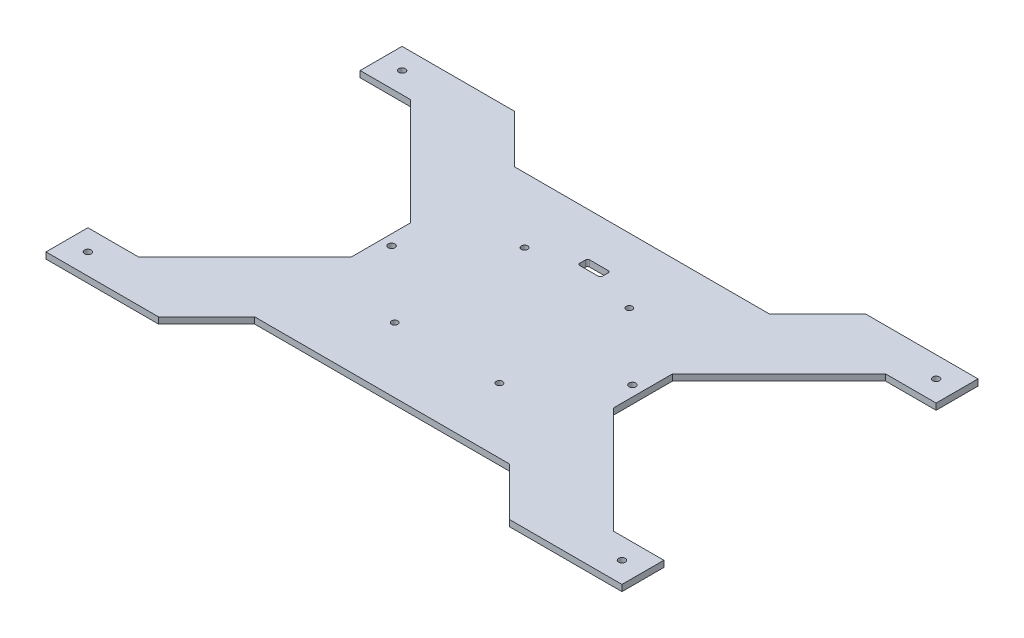
SolidWorks part; units mm, degrees
ref_plane "Front Plane" through (0, 0, 0) normal (0, 0, 1) x (1, 0, 0)
ref_plane "Top Plane" through (0, 0, 0) normal (0, 1, 0) x (1, 0, 0)
ref_plane "Right Plane" through (0, 0, 0) normal (1, 0, 0) x (0, 0, -1)
sketch "Sketch1" plane through (0, 0, 0) normal (0, -1, 0) x (1, 0, 0)
  line L0 (2.6321, -227.497) -> (-21.5101, -227.497)
  line L1 (-21.5101, -282.497) -> (-21.5101, 7.503) construction
  line L2 (-21.5101, -227.497) -> (-21.5101, -207.497)
  line L3 (-21.5101, -207.497) -> (32.1295, -207.497)
  line L4 (32.1295, -207.497) -> (55.0921, -230.4596)
  line L5 (55.0921, -230.4596) -> (176.8877, -230.4596)
  line L6 (53.4899, -292.497) -> (115.9899, -292.497) construction
  line L7 (115.9899, -230.4596) -> (115.9899, -292.497) construction
  line L8 (178.4899, -278.3549) -> (178.4899, -306.6392)
  line L9 (229.3478, -227.497) -> (178.4899, -278.3549)
  line L10 (253.4899, -227.497) -> (229.3478, -227.497)
  line L11 (253.4899, -207.497) -> (253.4899, -227.497)
  line L12 (199.8503, -207.497) -> (176.8877, -230.4596)
  line L13 (253.4899, -207.497) -> (199.8503, -207.497)
  line L14 (253.4899, -227.497) -> (253.4899, -207.497)
  line L15 (229.3478, -227.497) -> (253.4899, -227.497)
  line L16 (2.6321, -357.497) -> (53.4899, -306.6392)
  line L17 (-21.5101, -357.497) -> (2.6321, -357.497)
  line L18 (-21.5101, -377.497) -> (-21.5101, -357.497)
  line L19 (229.3478, -357.497) -> (253.4899, -357.497)
  line L20 (253.4899, -357.497) -> (253.4899, -377.497)
  line L21 (253.4899, -377.497) -> (199.8503, -377.497)
  line L22 (199.8503, -377.497) -> (176.8877, -354.5345)
  line L23 (253.4899, -377.497) -> (253.4899, -357.497)
  line L24 (253.4899, -357.497) -> (229.3478, -357.497)
  line L25 (229.3478, -357.497) -> (178.4899, -306.6392)
  line L26 (55.0921, -354.5345) -> (176.8877, -354.5345)
  line L27 (-21.5101, -357.497) -> (-21.5101, -432.2845)
  line L28 (-21.5101, -432.2845) -> (45.9899, -432.2845)
  line L29 (45.9899, -432.2845) -> (65.9899, -412.2845)
  line L30 (65.9899, -412.2845) -> (165.9899, -412.2845)
  line L31 (165.9899, -412.2845) -> (185.9899, -432.2845)
  line L32 (185.9899, -432.2845) -> (253.4899, -432.2845)
  line L33 (253.4899, -432.2845) -> (253.4899, -357.497)
  line L34 (253.4899, -357.497) -> (229.3478, -357.497)
  line L35 (229.3478, -357.497) -> (178.4899, -306.6392)
  line L36 (178.4899, -306.6392) -> (178.4899, -278.3549)
  line L37 (178.4899, -278.3549) -> (229.3478, -227.497)
  line L38 (229.3478, -227.497) -> (253.4899, -227.497)
  line L39 (253.4899, -227.497) -> (253.4899, -152.7096)
  line L40 (253.4899, -152.7096) -> (185.9899, -152.7096)
  line L41 (185.9899, -152.7096) -> (165.9899, -172.7096)
  line L42 (165.9899, -172.7096) -> (65.9899, -172.7096)
  line L43 (65.9899, -172.7096) -> (45.9899, -152.7096)
  line L44 (45.9899, -152.7096) -> (-21.5101, -152.7096)
  line L45 (-21.5101, -152.7096) -> (-21.5101, -227.497)
  line L46 (-21.5101, -227.497) -> (2.6321, -227.497)
  line L47 (2.6321, -227.497) -> (53.4899, -278.3549)
  line L48 (53.4899, -278.3549) -> (53.4899, -306.6392)
  line L49 (53.4899, -306.6392) -> (2.6321, -357.497)
  line L50 (2.6321, -357.497) -> (-21.5101, -357.497)
  line L69 (-21.5101, -207.497) -> (-21.5101, -227.497)
  line L70 (-21.5101, -227.497) -> (2.6321, -227.497)
  line L71 (2.6321, -227.497) -> (53.4899, -278.3549)
  line L72 (53.4899, -278.3549) -> (53.4899, -306.6392)
  line L75 (32.1295, -377.497) -> (55.0921, -354.5345)
  line L76 (-21.5101, -377.497) -> (32.1295, -377.497)
  line L77 (-21.5101, -357.497) -> (-21.5101, -377.497)
  line L78 (2.6321, -357.497) -> (-21.5101, -357.497)
  circle A0 centre (-11.5101, -217.497) radius 1.6
  circle A1 centre (243.4899, -217.497) radius 1.6
  circle A2 centre (243.4899, -367.497) radius 1.6
  circle A3 centre (-11.5101, -367.497) radius 1.6
  circle A4 centre (58.4899, -292.497) radius 1.6
  circle A5 centre (173.4899, -292.497) radius 1.6
  point P50 (178.4899, -292.497)
  line M31 (-1.5101, -302.497) -> (233.4899, -302.497)
  line M32 (233.4899, -302.497) -> (233.4899, -592.497)
  line M34 (-1.5101, -592.497) -> (-1.5101, -302.497)
  line M35 (233.4899, -282.497) -> (-1.5101, -282.497)
  line M36 (-1.5101, -282.497) -> (-1.5101, 7.503)
  line M38 (233.4899, 7.503) -> (233.4899, -282.497)
  line M39 (-21.5101, 7.503) -> (-21.5101, -282.497)
  line M43 (-21.5101, -302.497) -> (-21.5101, -592.497)
  line M49 (253.4899, -592.497) -> (253.4899, -302.497)
  line M53 (253.4899, -282.497) -> (253.4899, 7.503)
  dimension "D4" = 3.2
  dimension "D5" = 5
  dimension "D6" = 5
  dimension "D2" = 20
  dimension "D3" = 35
  dimension "D1" = 0
extrude "Extrude2" add sketch "Sketch1" along normal blind 3 contours L76 L17 A3 M43 M34 | L76 L75 L26 L22 L21 L19 L25 L8 L72 L16 L17 M34 M32 M31 | L21 L19 A2 M49 M32 | L72 L8 A5 A4 M35 M31 | L71 L72 L8 L9 L10 L13 L12 L5 L4 L3 L0 M35 M38 M36 | L3 L0 A0 M39 M36 | L13 L10 A1 M53 M38 region at (115.9899, 0, -247.4505) region at (-11.5101, 0, -227.2142) region at (115.9899, 0, -292.497) region at (115.9899, 0, -337.5436) region at (-1.7929, 0, -367.497) region at (233.7728, 0, -217.497) region at (243.4899, 0, -357.7799)
sketch "Sketch4" plane through (0, -3, 0) normal (0, -1, 0) x (1, 0, 0)
  line L0 (121.3899, -332.9844) -> (121.3899, -330.2844) construction
  line L1 (120.3899, -329.2844) -> (111.5899, -329.2844) construction
  line L2 (111.5899, -333.9844) -> (120.3899, -333.9844) construction
  line L3 (110.5899, -330.2844) -> (110.5899, -332.9844) construction
  line L4 (121.3899, -332.9844) -> (121.3899, -330.2844)
  line L5 (120.3899, -329.2844) -> (111.5899, -329.2844)
  line L6 (111.5899, -333.9844) -> (120.3899, -333.9844)
  line L7 (110.5899, -330.2844) -> (110.5899, -332.9844)
  arc A0 (121.3899, -330.2844) -> (120.3899, -329.2844) centre (120.3899, -330.2844) ccw construction
  arc A1 (120.3899, -333.9844) -> (121.3899, -332.9844) centre (120.3899, -332.9844) ccw construction
  arc A2 (110.5899, -332.9844) -> (111.5899, -333.9844) centre (111.5899, -332.9844) ccw construction
  arc A3 (111.5899, -329.2844) -> (110.5899, -330.2844) centre (111.5899, -330.2844) ccw construction
  arc A4 (142.4899, -261.497) -> (139.4899, -261.497) centre (140.9899, -261.497) ccw construction
  arc A5 (139.4899, -261.497) -> (142.4899, -261.497) centre (140.9899, -261.497) ccw construction
  arc A6 (139.4899, -323.497) -> (142.4899, -323.497) centre (140.9899, -323.497) ccw construction
  arc A7 (142.4899, -323.497) -> (139.4899, -323.497) centre (140.9899, -323.497) ccw construction
  arc A8 (92.4899, -261.497) -> (89.4899, -261.497) centre (90.9899, -261.497) ccw construction
  arc A9 (89.4899, -261.497) -> (92.4899, -261.497) centre (90.9899, -261.497) ccw construction
  arc A10 (92.4899, -323.497) -> (89.4899, -323.497) centre (90.9899, -323.497) ccw construction
  arc A11 (89.4899, -323.497) -> (92.4899, -323.497) centre (90.9899, -323.497) ccw construction
  arc A12 (121.3899, -330.2844) -> (120.3899, -329.2844) centre (120.3899, -330.2844) ccw
  arc A13 (120.3899, -333.9844) -> (121.3899, -332.9844) centre (120.3899, -332.9844) ccw
  arc A14 (110.5899, -332.9844) -> (111.5899, -333.9844) centre (111.5899, -332.9844) ccw
  arc A15 (111.5899, -329.2844) -> (110.5899, -330.2844) centre (111.5899, -330.2844) ccw
  arc A16 (142.4899, -261.497) -> (139.4899, -261.497) centre (140.9899, -261.497) ccw
  arc A17 (139.4899, -261.497) -> (142.4899, -261.497) centre (140.9899, -261.497) ccw
  arc A18 (139.4899, -323.497) -> (142.4899, -323.497) centre (140.9899, -323.497) ccw
  arc A19 (142.4899, -323.497) -> (139.4899, -323.497) centre (140.9899, -323.497) ccw
  arc A20 (92.4899, -261.497) -> (89.4899, -261.497) centre (90.9899, -261.497) ccw
  arc A21 (89.4899, -261.497) -> (92.4899, -261.497) centre (90.9899, -261.497) ccw
  arc A22 (92.4899, -323.497) -> (89.4899, -323.497) centre (90.9899, -323.497) ccw
  arc A23 (89.4899, -323.497) -> (92.4899, -323.497) centre (90.9899, -323.497) ccw
extrude "Cut-Extrude4" cut sketch "Sketch4" against normal blind 3
